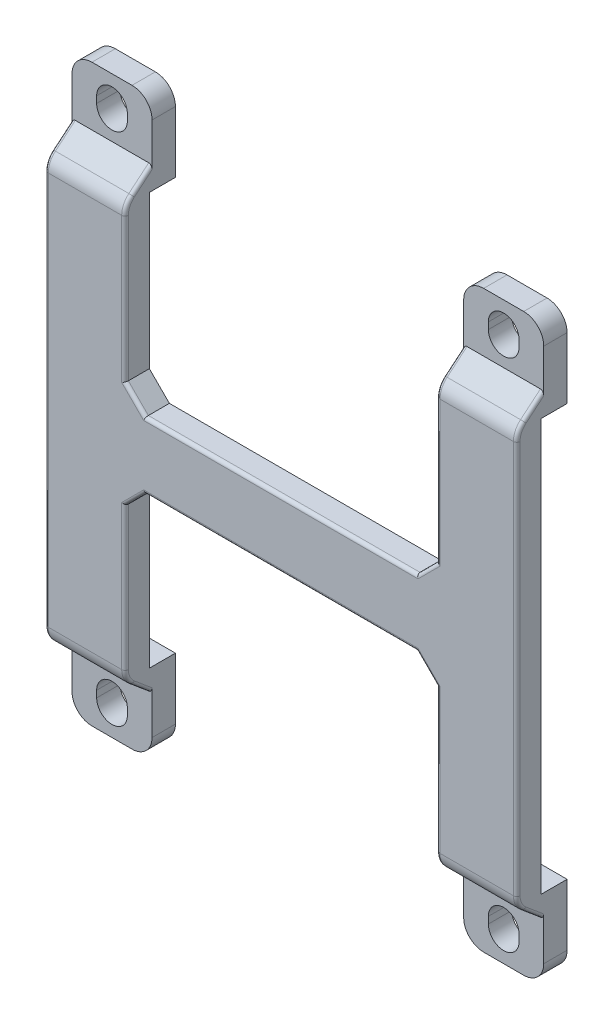
SolidWorks part; units mm, degrees
ref_plane "Front Plane" through (0, 0, 0) normal (0, 0, 1) x (1, 0, 0)
ref_plane "Top Plane" through (0, 0, 0) normal (0, 1, 0) x (1, 0, 0)
ref_plane "Right Plane" through (0, 0, 0) normal (1, 0, 0) x (0, 0, -1)
sketch "Sketch1" plane through (0, 0, 0) normal (0, 0, 1) x (1, 0, 0)
  line L0 (-44.8726, 37.3715) -> (-32.8726, 37.3715)
  line L1 (-44.8726, 37.3715) -> (-44.8726, 27.3715)
  line L2 (-44.8726, 27.3715) -> (-32.8726, 27.3715)
  line L3 (-32.8726, 37.3715) -> (-32.8726, 27.3715)
  line L4 (-44.8726, 37.3715) -> (-32.8726, 27.3715) construction
  line L5 (-44.8726, 27.3715) -> (-32.8726, 37.3715) construction
  line L6 (13.8274, 37.3715) -> (25.8274, 37.3715)
  line L7 (13.8274, 37.3715) -> (13.8274, 27.3715)
  line L8 (13.8274, 27.3715) -> (25.8274, 27.3715)
  line L9 (25.8274, 37.3715) -> (25.8274, 27.3715)
  line L10 (13.8274, 37.3715) -> (25.8274, 27.3715) construction
  line L11 (13.8274, 27.3715) -> (25.8274, 37.3715) construction
  line L12 (-44.8726, -38.7785) -> (-32.8726, -38.7785)
  line L13 (-44.8726, -38.7785) -> (-44.8726, -48.7785)
  line L14 (-44.8726, -48.7785) -> (-32.8726, -48.7785)
  line L15 (-32.8726, -38.7785) -> (-32.8726, -48.7785)
  line L16 (-44.8726, -38.7785) -> (-32.8726, -48.7785) construction
  line L17 (-44.8726, -48.7785) -> (-32.8726, -38.7785) construction
  line L18 (13.8274, -38.7785) -> (25.8274, -38.7785)
  line L19 (13.8274, -38.7785) -> (13.8274, -48.7785)
  line L20 (13.8274, -48.7785) -> (25.8274, -48.7785)
  line L21 (25.8274, -38.7785) -> (25.8274, -48.7785)
  line L22 (13.8274, -38.7785) -> (25.8274, -48.7785) construction
  line L23 (13.8274, -48.7785) -> (25.8274, -38.7785) construction
  line L24 (-44.8726, 27.3715) -> (-44.8726, -38.7785)
  line L25 (-32.8726, -38.7785) -> (-32.8726, 27.3715)
  line L26 (13.8274, 27.3715) -> (13.8274, -38.7785)
  line L27 (25.8274, 27.3715) -> (25.8274, -38.7785)
  line L28 (-32.8726, -5.7035) -> (13.8274, -5.7035) construction
  line L29 (-44.8726, -0.7035) -> (25.8274, -0.7035)
  line L30 (-44.8726, -0.7035) -> (-44.8726, -10.7035)
  line L31 (-44.8726, -10.7035) -> (25.8274, -10.7035)
  line L32 (25.8274, -0.7035) -> (25.8274, -10.7035)
  line L33 (-44.8726, -0.7035) -> (25.8274, -10.7035) construction
  line L34 (-44.8726, -10.7035) -> (25.8274, -0.7035) construction
  line L35 (-38.8726, 32.3715) -> (-38.8726, 33.3715) construction
  line L36 (-41.1726, 32.3715) -> (-41.1726, 33.3715)
  line L37 (-36.5726, 32.3715) -> (-36.5726, 33.3715)
  line L38 (-9.5226, -5.7035) -> (-9.5226, 17.21) construction
  line L39 (19.8274, 32.3715) -> (19.8274, 33.3715) construction
  line L40 (17.5274, 32.3715) -> (17.5274, 33.3715)
  line L41 (22.1274, 32.3715) -> (22.1274, 33.3715)
  line L42 (-38.8726, -43.7785) -> (-38.8726, -44.7785) construction
  line L43 (-36.5726, -43.7785) -> (-36.5726, -44.7785)
  line L44 (-41.1726, -43.7785) -> (-41.1726, -44.7785)
  line L45 (19.8274, -43.7785) -> (19.8274, -44.7785) construction
  line L46 (22.1274, -43.7785) -> (22.1274, -44.7785)
  line L47 (17.5274, -43.7785) -> (17.5274, -44.7785)
  circle A0 centre (-38.8726, 32.3715) radius 2.3
  circle A1 centre (19.8274, 32.3715) radius 2.3
  circle A2 centre (-38.8726, -43.7785) radius 2.3
  circle A3 centre (19.8274, -43.7785) radius 2.3
  circle A4 centre (-38.8726, 32.3715) radius 2.8702 construction
  circle A5 centre (19.8274, 32.3715) radius 2.8702 construction
  circle A6 centre (-38.8726, -43.7785) radius 2.8702 construction
  circle A7 centre (19.8274, -43.7785) radius 2.8702 construction
  arc A8 (-41.1726, 32.3715) -> (-36.5726, 32.3715) centre (-38.8726, 32.3715) ccw
  arc A9 (-36.5726, 33.3715) -> (-41.1726, 33.3715) centre (-38.8726, 33.3715) ccw
  arc A10 (17.5274, 32.3715) -> (22.1274, 32.3715) centre (19.8274, 32.3715) ccw
  arc A11 (22.1274, 33.3715) -> (17.5274, 33.3715) centre (19.8274, 33.3715) ccw
  arc A12 (-36.5726, -43.7785) -> (-41.1726, -43.7785) centre (-38.8726, -43.7785) ccw
  arc A13 (-41.1726, -44.7785) -> (-36.5726, -44.7785) centre (-38.8726, -44.7785) ccw
  arc A14 (22.1274, -43.7785) -> (17.5274, -43.7785) centre (19.8274, -43.7785) ccw
  arc A15 (17.5274, -44.7785) -> (22.1274, -44.7785) centre (19.8274, -44.7785) ccw
  point P26 (-9.5226, -5.7035)
  point P31 (-38.8726, 32.8715)
  point P48 (19.8274, 32.8715)
  point P54 (-38.8726, -44.2785)
  point P61 (19.8274, -44.2785)
  dimension "D1" = 4.6
  dimension "D2" = 12
  dimension "D3" = 10
  dimension "D4" = 10
  dimension "D5" = 1
extrude "Boss-Extrude1" add sketch "Sketch1" along normal blind 3 and the other way blind 4.55 contours L3 L0 L1 L2 A0 | L24 L29 L25 L2 | L24 L31 L25 L29 | L31 L24 L12 L25 | L15 L12 L13 L14 A2 | L31 L26 L18 L27 | L21 L18 L19 L20 A3 | L26 L31 L27 L29 | L25 L31 L26 L29 | L26 L29 L27 L8 | L9 L6 L7 L8 A1 region at (-38.8726, 37.2153, 0) region at (-38.8726, 13.334, 0) region at (-38.8726, -5.7035, 0) region at (-9.5226, -5.7035, 0) region at (-38.8726, -24.741, 0) region at (19.8274, -5.7035, 0) region at (19.8274, 13.334, 0) region at (-38.8726, -38.9347, 0) region at (19.8274, -24.741, 0) region at (13.9836, 32.3715, 0) region at (19.8274, -38.9347, 0)
sketch "Sketch5" plane through (0, 0, -4.55) normal (0, 0, -1) x (-1, 0, 0)
  line L0 (-25.8274, 37.3715) -> (-25.8274, -48.7785) construction
  line L1 (-25.8274, 25.1715) -> (-13.8274, 25.1715)
  line L2 (-25.8274, 25.1715) -> (-25.8274, -36.5695)
  line L3 (-25.8274, -36.5695) -> (-13.8274, -36.5695)
  line L4 (-13.8274, 25.1715) -> (-13.8274, -36.5695)
  line L5 (32.8726, 25.1715) -> (44.8726, 25.1715)
  line L6 (32.8726, 25.1715) -> (32.8726, -36.5695)
  line L7 (32.8726, -36.5695) -> (44.8726, -36.5695)
  line L8 (44.8726, 25.1715) -> (44.8726, -36.5695)
  line L9 (-25.8274, -0.7035) -> (44.8726, -0.7035)
  line L10 (-25.8274, -0.7035) -> (-25.8274, -10.7035)
  line L11 (-25.8274, -10.7035) -> (44.8726, -10.7035)
  line L12 (44.8726, -0.7035) -> (44.8726, -10.7035)
  line L13 (-31.8234, 25.1715) -> (50.8726, 25.1715) construction
  line L14 (32.8726, 37.3715) -> (32.8726, -0.7035) construction
  line L15 (-13.8274, -10.7035) -> (-13.8274, -48.7785) construction
  line L16 (-25.8274, 37.3715) -> (-25.8274, -48.7785) construction
  line L17 (-26.1321, -36.5695) -> (-31.8234, -36.5695) construction
  line L18 (44.8726, 37.3715) -> (44.8726, -48.7785) construction
  line L19 (50.8726, -36.5695) -> (45.1812, -36.5695) construction
  line M2 (32.8726, 37.3715) -> (32.8726, -0.7035)
  line M3 (32.8726, -0.7035) -> (-13.8274, -0.7035)
  line M4 (-13.8274, -0.7035) -> (-13.8274, 37.3715)
  line M6 (-25.8274, 37.3715) -> (-25.8274, -48.7785)
  line M8 (-13.8274, -48.7785) -> (-13.8274, -10.7035)
  line M9 (-13.8274, -10.7035) -> (32.8726, -10.7035)
  line M10 (32.8726, -10.7035) -> (32.8726, -48.7785)
  line M12 (44.8726, -48.7785) -> (44.8726, 37.3715)
extrude "Cut-Extrude1" cut sketch "Sketch5" against normal blind 3.9 contours L9 L1 M6 M4 | L2 L11 L4 L9 | L11 L3 M6 M8 | L6 L4 M3 M9 | L6 L11 L8 L9 | L11 L7 M10 M12 | L9 L8 L5 M2 region at (19.8274, 12.234, -4.55) region at (19.8274, -5.7035, -4.55) region at (-9.5226, -5.7035, -4.55) region at (19.8274, -23.6365, -4.55) region at (-38.8726, -5.7035, -4.55) region at (-38.8726, 12.234, -4.55) region at (-38.8726, -23.6365, -4.55)
sketch "Sketch6" plane through (-44.8726, 0, 0) normal (-1, 0, 0) x (0, 0, 1)
  line L0 (3, 25.1715) -> (-1.05, 28.5698)
  line L1 (3, 37.3715) -> (3, -48.7785) construction
  line L2 (-0.65, -36.5785) -> (3, -36.5785) construction
  line L3 (-0.65, 25.1715) -> (3, 25.1715) construction
  line L4 (-1.05, 25.1715) -> (-1.05, 37.3715)
  line L5 (-0.65, 25.1715) -> (-4.55, 25.1715) construction
  line L6 (-4.55, 37.3715) -> (3, 37.3715) construction
  line L7 (-4.55, 37.3715) -> (-4.55, 25.1715) construction
  line L8 (-1.05, 37.3715) -> (3, 37.3715)
  line L9 (3, 37.3715) -> (3, 25.1715)
  line L10 (3, -5.7035) -> (0, -5.7035) construction
  line L12 (3, -48.7785) -> (3, -36.5785)
  line L13 (-1.05, -48.7785) -> (3, -48.7785)
  line L14 (-1.05, -36.5785) -> (-1.05, -48.7785)
  line L15 (3, -36.5785) -> (-1.05, -39.9769)
  line M9 (-4.55, -48.7785) -> (3, -48.7785)
  line M10 (3, -48.7785) -> (3, 37.3715)
  line M11 (3, 37.3715) -> (-4.55, 37.3715)
  dimension "D1" = 3.5
  dimension "D2" = 50
extrude "Cut-Extrude2" cut sketch "Sketch6" against normal through all contours L4 L0 M10 M11 | L15 L14 M10 M9 region at (-44.8726, 32.0753, 1.0842) region at (-44.8726, -43.4823, 1.0842)
chamfer "Chamfer1" distance 3 angle 45 4 edges at (-32.8726, -10.7035, 1.175) (-32.8726, -0.7035, 1.175) (13.8274, -10.7035, 1.175) (13.8274, -0.7035, 1.175)
fillet "Fillet1" radius 3 8 edges at (25.8274, -48.7785, -2.8) (13.8274, -48.7785, -2.8) (-32.8726, -48.7785, -2.8) (-44.8726, -48.7785, -2.8) (25.8274, 37.3715, -2.8) (13.8274, 37.3715, -2.8) (-32.8726, 37.3715, -2.8) (-44.8726, 37.3715, -2.8)
fillet "Fillet2" radius 3 4 edges at (19.8274, -36.5785, 3) (-38.8726, -36.5785, 3) (19.8274, 25.1715, 3) (-38.8726, 25.1715, 3)
fillet "Fillet3" radius 0.5 28 edges at (-32.8726, -38.7273, 0.4392) (-32.8726, -36.4474, 2.7189) (-44.8726, 27.3203, 0.4392) (-44.8726, 25.0404, 2.7189) (-44.8726, -38.7273, 0.4392) (-44.8726, -36.4474, 2.7189) (-32.8726, 27.3203, 0.4392) (-32.8726, 25.0404, 2.7189) (13.8274, 27.3203, 0.4392) (13.8274, 25.0404, 2.7189) (25.8274, 27.3203, 0.4392) (25.8274, 25.0404, 2.7189) (25.8274, -38.7273, 0.4392) (25.8274, -36.4474, 2.7189) (13.8274, -38.7273, 0.4392) (13.8274, -36.4474, 2.7189) (12.3274, -12.2035, 3) (-9.5226, -10.7035, 3) (-31.3726, -12.2035, 3) (-32.8726, -24.4415, 3) (-44.8726, -5.7035, 3) (-32.8726, 13.0345, 3) (-31.3726, 0.7965, 3) (-9.5226, -0.7035, 3) (12.3274, 0.7965, 3) (13.8274, 13.0345, 3) (25.8274, -5.7035, 3) (13.8274, -24.4415, 3)
equation "\"D2@Boss-Extrude1\"=4.55"
